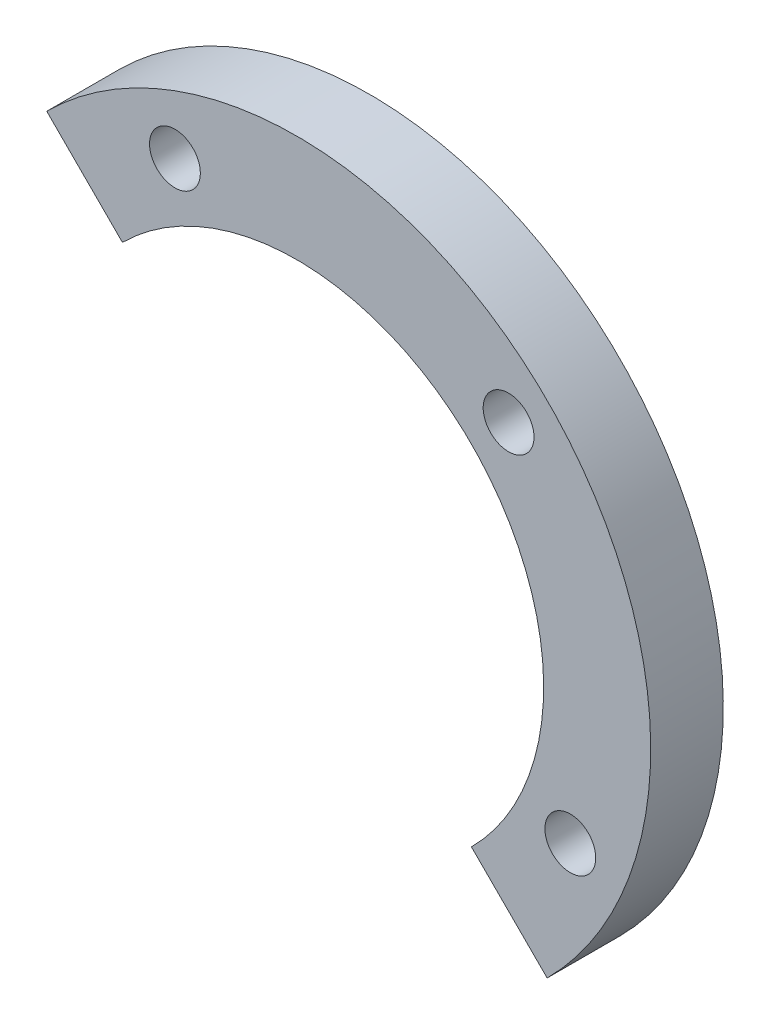
SolidWorks part; units mm, degrees
ref_plane "Front Plane" through (0, 0, 0) normal (0, 0, 1) x (1, 0, 0)
ref_plane "Top Plane" through (0, 0, 0) normal (0, 1, 0) x (1, 0, 0)
ref_plane "Right Plane" through (0, 0, 0) normal (1, 0, 0) x (0, 0, -1)
sketch "Sketch1" plane through (0, 0, 0) normal (0, 0, 1) x (1, 0, 0)
  line L0 (78.7927, 51.2155) -> (74.6195, 55.3862)
  line L2 (51.2155, 78.7927) -> (55.3862, 74.6195)
  arc A0 (78.7927, 51.2155) -> (51.2155, 78.7927) centre (65, 65) ccw construction
  arc A1 (78.7927, 51.2155) -> (51.2155, 78.7927) centre (65, 65) ccw
  circle A2 centre (58.2805, 80.0698) radius 1.4 construction
  circle A3 centre (76.6673, 76.6673) radius 1.4 construction
  circle A4 centre (80.0698, 58.2805) radius 1.4 construction
  circle A5 centre (58.2805, 80.0698) radius 1.4
  circle A6 centre (76.6673, 76.6673) radius 1.4
  circle A7 centre (80.0698, 58.2805) radius 1.4
  circle A8 centre (65, 65) radius 13.6
  circle A9 centre (65, 65) radius 13.5 construction
  dimension "D1" = 0.1
extrude "Shape" add sketch "Sketch1" along normal blind 4 contours A8 L0 A1 L2 A7 A6 A5 region at (77.0388, 53.6338, 0)
sketch "Sketch2" plane through (0, 0, 0) normal (0, 0, 1) x (1, 0, 0)
  line L0 (53.3009, 76.7061) -> (58.2805, 80.0698) construction
  line L1 (60.9171, 81.2454) -> (58.5807, 82.9409)
  line L2 (58.5807, 82.9409) -> (55.9442, 81.7653)
  line L3 (55.9442, 81.7653) -> (55.644, 78.8942)
  line L4 (55.644, 78.8942) -> (57.9804, 77.1987)
  line L5 (57.9804, 77.1987) -> (60.6169, 78.3743)
  line L6 (60.6169, 78.3743) -> (60.9171, 81.2454)
  line L7 (51.2155, 78.7927) -> (55.3862, 74.6195) construction
  line L8 (50.6905, 79.9702) -> (63.4271, 85.6493) construction
  line L9 (58.2805, 80.0698) -> (57.0588, 82.8098) construction
  line L10 (55.9442, 81.7653) -> (55.7405, 82.222) construction
  line L11 (58.5807, 82.9409) -> (58.3771, 83.3976) construction
  line L12 (58.2805, 80.0698) -> (76.6673, 76.6673) construction
  line L13 (51.2155, 78.7927) -> (50.6905, 79.9702) construction
  line L14 (63.4271, 85.6493) -> (63.9522, 84.4718) construction
  line L15 (55.644, 78.8942) -> (60.9171, 81.2454) construction
  circle A0 centre (58.2805, 80.0698) radius 2.5 construction
  arc A1 (78.7927, 51.2155) -> (51.2155, 78.7927) centre (65, 65) ccw construction
  circle A2 centre (56.5573, 79.3014) radius 1
  circle A3 centre (56.7535, 81.178) radius 1
  circle A4 centre (58.4767, 81.9463) radius 1
  circle A5 centre (60.0037, 80.8382) radius 1
  circle A6 centre (59.8076, 78.9616) radius 1
  circle A7 centre (58.0843, 78.1933) radius 1
  point P21 (0, 0)
  point P28 (0, 0)
  point P39 (58.2805, 80.0698)
  dimension "D2" = 2
  dimension "D1" = 5
  dimension "D3" = 6
extrude "Nut cuts" cut sketch "Sketch2" along normal blind 2 contours A3 | A4 | A5 | A6 | A7 | A2 | L5 L6 L1 L2 L3 L4
